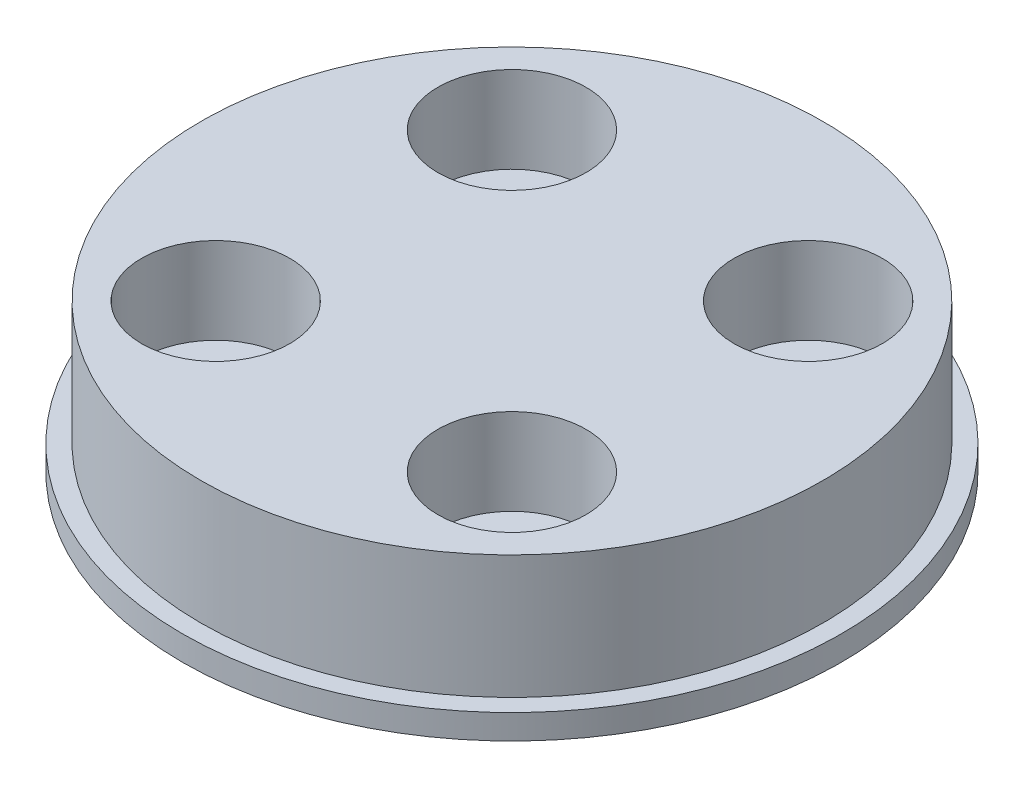
SolidWorks part; units mm, degrees
material "ABS"
ref_plane "Front Plane" through (0, 0, 0) normal (0, 0, 1) x (1, 0, 0)
ref_plane "Top Plane" through (0, 0, 0) normal (0, 1, 0) x (1, 0, 0)
ref_plane "Right Plane" through (0, 0, 0) normal (1, 0, 0) x (0, 0, -1)
sketch "Sketch1" plane through (0, 33, 0) normal (0, 1, 0) x (1, 0, 0)
  circle A0 centre (0, 0) radius 12.6
  circle A1 centre (0, 0) radius 13.35
  circle A2 centre (-6, 6) radius 1.575
  circle A3 centre (6, 6) radius 1.575
  circle A4 centre (6, -6) radius 1.575
  circle A5 centre (-6, -6) radius 1.575
  point P16 (0, 0)
  circle M2 centre (-6, -6) radius 1.575
  circle M3 centre (6, -6) radius 1.575
  circle M4 centre (6, 6) radius 1.575
  circle M5 centre (-6, 6) radius 1.575
  dimension "D1" = 3.15
  dimension "D3" = 25.2
  dimension "D4" = 26.7
  dimension "D2" = 4
extrude "Boss-Extrude1" add sketch "Sketch1" along normal blind 1 contours A0 M3 M5 M4 M2 | A1 A0 region at (0, 33, 0) region at (-12.9724, 33, 0)
extrude "Boss-Extrude2" add sketch "Sketch1<3>" along normal blind 6 contours A0 M3 M5 M4 M2 region at (0, 33, 0)
sketch "Sketch1<3>" plane through (0, 33, 0) normal (0, 1, 0) x (1, 0, 0) same geometry as "Sketch1"
sketch "Sketch2" plane through (0, 39, 0) normal (0, 1, 0) x (1, 0, 0)
  circle A0 centre (-6, 6) radius 3
  circle A1 centre (6, 6) radius 3
  circle A2 centre (6, -6) radius 3
  circle A3 centre (-6, -6) radius 3
  point P12 (0, 0)
  dimension "D1" = 6
  dimension "D2" = 4
extrude "Cut-Extrude1" cut sketch "Sketch2" against normal blind 3.5
equation "\"RingPinShaft\"= 5.05"
equation "\"CenterBearingOut\"=32.00"
equation "\"OutputBearingOut\"=37.00"
equation "\"RingPostIn\"=5.15"
equation "\"CamBearingOut\"=15.1"
equation "\"DiskOutputShaft\"=10.1"
equation "\"CenterShaft\"=25.2"
equation "\"Eccentricity\"=2"
equation "\"CycCamShaft\"=10.05"
equation "\"m3Thru\"=3.15"
equation "\"m3Insert\"=4.2"
equation "\"D1@Sketch1\"=\"m3Thru\""
equation "\"D3@Sketch1\"=\"CenterShaft\""
equation "\"D4@Sketch1\"=\"CenterShaft\"+1.5"
